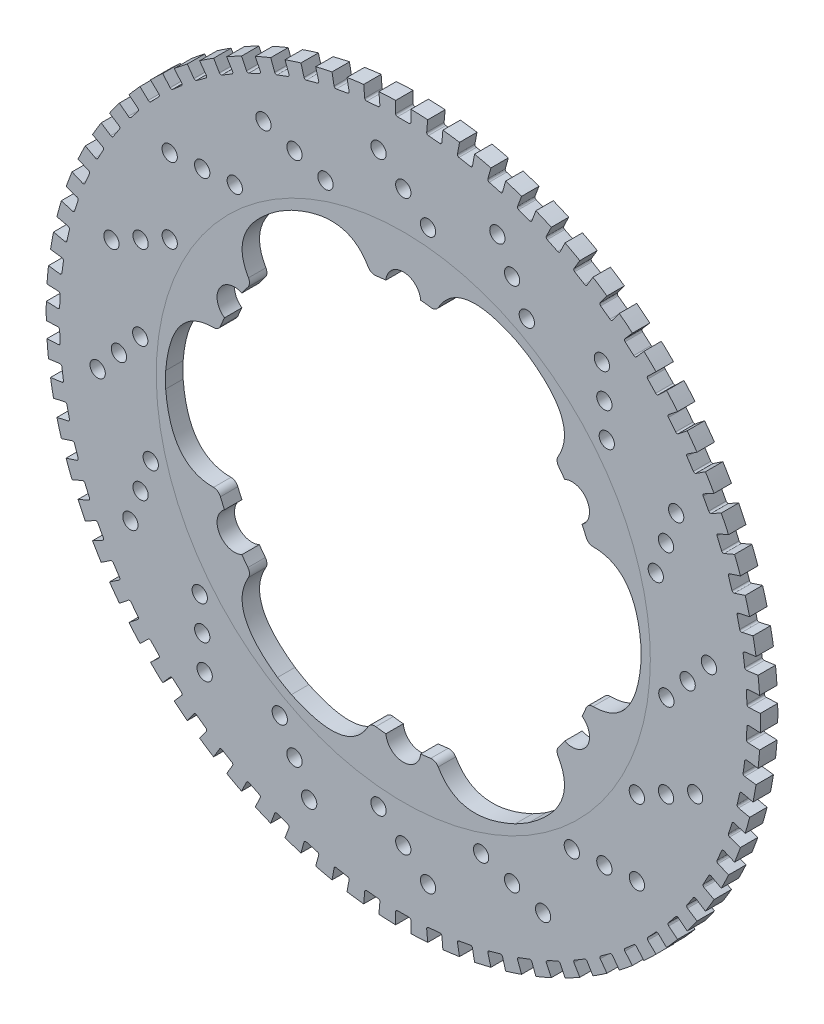
SolidWorks part; units mm, degrees
ref_plane "Front Plane" through (0, 0, 0) normal (0, 0, 1) x (1, 0, 0)
ref_plane "Top Plane" through (0, 0, 0) normal (0, 1, 0) x (1, 0, 0)
ref_plane "Right Plane" through (0, 0, 0) normal (1, 0, 0) x (0, 0, -1)
sketch "Sketch2" plane through (0, 0, 0) normal (0, 0, 1) x (1, 0, 0)
  circle A0 centre (0, 0) radius 95.25
  circle A1 centre (0, 0) radius 64.77
  circle A2 centre (0, 0) radius 53.086 construction
  dimension "D1" = 190.5
  dimension "D2" = 30.48
  dimension "D3" = 106.172
extrude "RotorSwept" add sketch "Sketch2" along normal blind 4.7498
sketch "Sketch3" plane through (0, 0, 4.7498) normal (0, 0, 1) x (1, 0, 0)
  line L0 (0, 53.086) -> (0, 64.77) construction
  circle A0 centre (0, 0) radius 53.086 construction
  circle A1 centre (0, 53.086) radius 4.7625
  circle A2 centre (0, 0) radius 53.721
  circle A3 centre (0, 0) radius 64.77 construction
  spline S0 degree 2 poles (-8.89, 52.9803) (-14.4253, 64.6738) (-30.48, 57.15) knots 0 0 0 1 1 1
  spline S1 degree 2 poles (8.89, 52.9803) (14.4253, 64.6738) (30.48, 57.15) knots 0 0 0 1 1 1
  circle M3 centre (0, 0) radius 64.77
  dimension "D1" = 106.172
  dimension "D2" = 9.525
  dimension "D5" = 11.43
  dimension "D4" = 8.89
  dimension "D6" = 30.48
  dimension "D7" = 3.81
  dimension "D3" = 0.635
extrude "FloatPinIF" add sketch "Sketch3" along direction (0, 0, 1) on the side against the normal through all contours A2 S1 S0 A1 M3 region at (0, 59.9234, 4.7498)
pattern_circular "FloatPinPattern" count 6 over 360 about axis through (0, 0, 4.7498) along (0, 0, -1) of "FloatPinIF" reverse direction yes
sketch "Sketch4" plane through (0, 0, 4.7498) normal (0, 0, 1) x (1, 0, 0)
  line L0 (-6.7401, 83.2668) -> (6.7401, 71.6732) construction
  line L1 (0, 0) -> (-6.7401, 83.2668) construction
  line L2 (6.7401, 71.6732) -> (0, 0) construction
  circle A0 centre (0, 0) radius 67.31 construction
  circle A1 centre (0, 0) radius 95.25 construction
  circle A2 centre (0, 0) radius 92.71 construction
  circle A3 centre (0, 0) radius 77.47 construction
  circle A4 centre (0, 77.47) radius 2.0828
  circle A5 centre (-6.7401, 83.2668) radius 2.0828
  circle A6 centre (6.7401, 71.6732) radius 2.0828
  point P13 (0, 77.47)
  dimension "D1" = 27.94
  dimension "D4" = 4.1656
  dimension "D6" = 4.1656
  dimension "D7" = 4.1656
  dimension "D5" = 17.78
  dimension "D8" = 10
  dimension "D2" = 25.4
  dimension "D3" = 10.16
extrude "Holes" cut sketch "Sketch4" against normal through all
pattern_circular "HolesPattern" count 16 over 360 about axis through (0, 0, 4.7498) along (0, 0, -1) of "Holes" reverse direction yes
sketch "Sketch6" plane through (0, 0, 4.7498) normal (0, 0, 1) x (1, 0, 0)
  line L0 (-95.25, 0) -> (67.31, 0) construction
  line L1 (0, 0) -> (58.2922, 33.655) construction
  line L2 (58.2922, 33.655) -> (82.4889, 47.625)
  line L3 (67.31, 0) -> (95.25, 0)
  circle A0 centre (0, 0) radius 67.31
  circle A1 centre (0, 0) radius 95.25
  point P6 (58.2922, 33.655)
  point P9 (67.31, 0)
  dimension "D2" = 27.94
  dimension "D3" = 190.5
  dimension "D1" = 30
split line "SplitLine"
fillet "Fillet1" radius 2.032 12 edges at (-8.89, -52.9803, 2.3749) (8.89, -52.9803, 2.3749) (41.4373, -34.1891, 2.3749) (50.3273, -18.7912, 2.3749) (-50.3273, -18.7912, 2.3749) (-41.4373, -34.1891, 2.3749) (-41.4373, 34.1891, 2.3749) (-50.3273, 18.7912, 2.3749) (50.3273, 18.7912, 2.3749) (41.4373, 34.1891, 2.3749) (8.89, 52.9803, 2.3749) (-8.89, 52.9803, 2.3749)
sketch "Sketch8" plane through (0, 0, 4.7498) normal (0, 0, 1) x (1, 0, 0)
  circle A0 centre (0, 0) radius 97.282
  circle A1 centre (0, 0) radius 95.25
extrude "Boss-Extrude2" add sketch "Sketch8" against normal blind 4.7498
sketch "Sketch12" plane through (0, 0, 4.7498) normal (0, 0, 1) x (1, 0, 0)
  line L0 (0, 0) -> (0, 119.1942) construction
  line L1 (0, 98.0625) -> (0, 93.6498)
  line L2 (-2.0777, 93.6498) -> (2.0777, 93.6498)
  line L3 (2.0777, 93.6498) -> (2.0777, 98.0625)
  line L4 (0, 98.0625) -> (2.0777, 98.0625)
  line L5 (0, 98.0625) -> (-2.0777, 98.0625)
  line L6 (-2.0777, 93.6498) -> (-2.0777, 98.0625)
  dimension "D2" = 2.0777
extrude "Cut-Extrude8" cut sketch "Sketch12" against normal blind 4.826 contours L4 L1 L2 L3 | L6 L2 L1 L5 region at (1.0389, 95.8562, 4.7498) region at (-1.0389, 95.8562, 4.7498)
fillet "Fillet3" radius 0.508 2 edges at (2.0777, 93.6498, 2.3749) (-2.0777, 93.6498, 2.3749)
pattern_circular "CirPattern2" count 70 over 360 about axis through (0, 0, 4.7498) along (0, 0, 1) of "Cut-Extrude8", "Fillet3"
